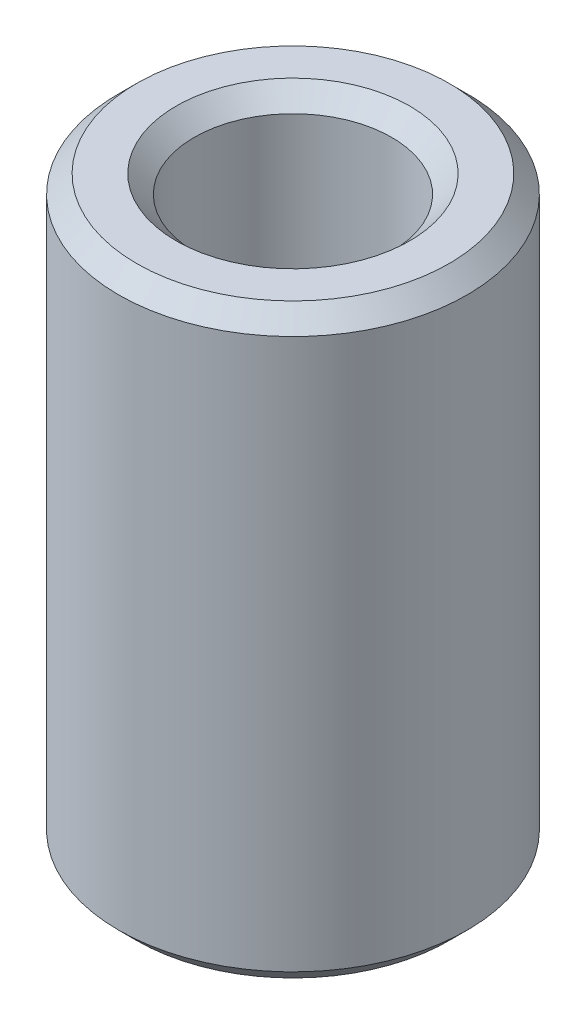
SolidWorks part; units mm, degrees
ref_plane "Front Plane" through (0, 0, 0) normal (0, 0, 1) x (1, 0, 0)
ref_plane "Top Plane" through (0, 0, 0) normal (0, 1, 0) x (1, 0, 0)
ref_plane "Right Plane" through (0, 0, 0) normal (1, 0, 0) x (0, 0, -1)
sketch "Sketch1" plane through (0, 0, 0) normal (0, 1, 0) x (1, 0, 0)
  circle A0 centre (0, 0) radius 5
  dimension "SLEEVE_OD" = 10
extrude "Boss-Extrude1" add sketch "Sketch1" along normal blind 16.8244
sketch "Sketch2" plane through (0, 0, 0) normal (0, 1, 0) x (1, 0, 0)
  circle A0 centre (0, 0) radius 2.8335
  dimension "BORE_D" = 5.6671
extrude "Cut-Extrude1" cut sketch "Sketch2" along normal through all
chamfer "Chamfer1" distance 0.5184 angle 45 4 edges at (0, 16.8244, 2.8335) (0, 0, 2.8335) (0, 0, 5) (0, 16.8244, 5)
